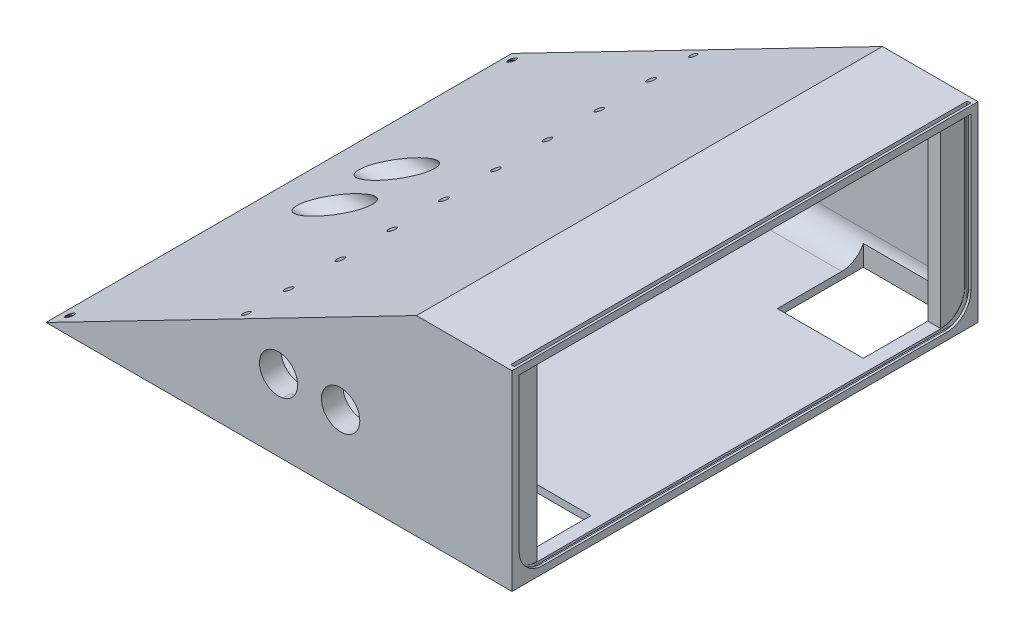
SolidWorks part; units mm, degrees
ref_plane "Front Plane" through (0, 0, 0) normal (0, 0, 1) x (1, 0, 0)
ref_plane "Top Plane" through (0, 0, 0) normal (0, 1, 0) x (1, 0, 0)
ref_plane "Right Plane" through (0, 0, 0) normal (1, 0, 0) x (0, 0, -1)
ref_plane "Plane1" through (0, 0, 0) normal (1, 0, 0) x (0, 0, -1)
ref_plane "Plane2" through (0, 0, 97.5) normal (0, 0, 1) x (1, 0, 0)
ref_plane "Plane3" through (1, 0, 0) normal (1, 0, 0) x (0, 0, -1)
ref_plane "Plane11" through (26, 0, 0) normal (1, 0, 0) x (0, 0, -1)
sketch "Sketch2" plane through (0, 0, 0) normal (0, 0, 1) x (1, 0, 0)
  line L0 (0, 0) -> (195, 0)
  line L1 (195, 0) -> (195, 80)
  line L2 (195, 80) -> (155, 80)
  line L3 (155, 80) -> (0, 0)
  dimension "D1" = 195
  dimension "D2" = 40
  dimension "80" = 80
extrude "Robot" add sketch "Sketch2" along normal blind 195
sketch "Sketch3" plane through (0, 0, 195) normal (0, 0, 1) x (1, 0, 0)
  line L0 (0, 0) -> (195, 0) construction
  circle A0 centre (97.2899, 30) radius 8.02
  circle A1 centre (123.2899, 30) radius 8.02
  dimension "D1" = 30
  dimension "D2" = 16.04
  dimension "D4" = 16.04
  dimension "D3" = 26
  dimension "D5" = 30
sketch "Arriba" plane through (0, 80, 0) normal (0, 1, 0) x (1, 0, 0)
  line L0 (195, 0) -> (195, -195) construction
  line L1 (0, 0) -> (0, -195) construction
  line L2 (0, -97.5) -> (195, -97.5) construction
  line L3 (0, 0) -> (195, 0) construction
  line L4 (0, -195) -> (195, -195) construction
  line L5 (97.5, 0) -> (97.5, -195) construction
sketch "Adelante" plane through (0, 0, 0) normal (1, 0, 0) x (0, 0, -1)
  line L0 (0, 80) -> (0, 0) construction
  line L1 (-97.5, 80) -> (-97.5, 0) construction
  line L2 (0, 80) -> (-195, 80) construction
  line L3 (-195, 0) -> (0, 0) construction
  line L4 (-195, 80) -> (-195, 0) construction
  line L5 (0, 0) -> (-195, 0) construction
sketch "Sketch9" plane through (0, 0, 0) normal (0, 0, -1) x (-1, 0, 0)
  line L1 (0, 0) -> (-195, 0) construction
  circle A0 centre (-97.284, 30) radius 8.2
  circle A1 centre (-123.284, 30) radius 8.2
  dimension "D2" = 16.4
  dimension "D4" = 30
  dimension "D6" = 16.4
  dimension "D3" = 30
  dimension "D5" = 26
sketch "Sketch10" plane through (0, 0, 0) normal (0, -1, 0) x (-1, 0, 0)
  line L0 (0, -195) -> (-195, -195) construction
  line L1 (-187, -191) -> (-150, -191)
  line L2 (-187, -191) -> (-187, -154)
  line L3 (-187, -154) -> (-150, -154)
  line L4 (-150, -191) -> (-150, -154)
  line L5 (-195, 0) -> (-195, -195) construction
  dimension "D1" = 4
  dimension "D2" = 8
  dimension "D3" = 37
  dimension "D4" = 37
sketch "Sketch12" plane through (0, 0, 0) normal (0, -1, 0) x (-1, 0, 0)
  line L0 (-195, 0) -> (-195, -195) construction
  line L1 (-187, -40) -> (-151, -40)
  line L2 (-187, -40) -> (-187, -4)
  line L3 (-187, -4) -> (-151, -4)
  line L4 (-151, -40) -> (-151, -4)
  line L5 (0, 0) -> (-195, 0) construction
  dimension "D1" = 8
  dimension "D2" = 4
  dimension "D3" = 36
  dimension "D4" = 36
sketch "Sketch13" plane through (0, 0, 0) normal (0, -1, 0) x (1, 0, 0)
  line L0 (0, 0) -> (195, 0) construction
  line L1 (26, 8) -> (33.1, 8)
  line L2 (26, 8) -> (26, 15.1)
  line L3 (26, 15.1) -> (33.1, 15.1)
  line L4 (33.1, 8) -> (33.1, 15.1)
  line L5 (0, 0) -> (0, 195) construction
  dimension "D1" = 8
  dimension "D2" = 26
  dimension "D3" = 7.1
  dimension "D4" = 7.1
sketch "Sketch14" plane through (0, 0, 0) normal (0, -1, 0) x (-1, 0, 0)
  line L0 (0, -195) -> (-195, -195) construction
  line L1 (-26, -179.9) -> (-33.1, -179.9)
  line L2 (-26, -179.9) -> (-26, -187)
  line L3 (-26, -187) -> (-33.1, -187)
  line L4 (-33.1, -179.9) -> (-33.1, -187)
  line L5 (0, 0) -> (0, -195) construction
  dimension "D1" = 8
  dimension "D2" = 26
  dimension "D3" = 7.1
  dimension "D4" = 7.1
sketch "Sketch15" plane through (0, 0, 0) normal (0, -1, 0) x (-1, 0, 0)
  line L0 (0, -97.5) -> (-195, -97.5) construction
  line L1 (-26, -93.95) -> (-33.1, -93.95)
  line L2 (-26, -93.95) -> (-26, -101.05)
  line L3 (-26, -101.05) -> (-33.1, -101.05)
  line L4 (-33.1, -93.95) -> (-33.1, -101.05)
  line L5 (0, 0) -> (0, -195) construction
  dimension "D1" = 3.55
  dimension "D2" = 3.55
  dimension "D3" = 7.1
  dimension "D4" = 26
shell "Vacio por dentro 3mm" thickness 3 removed face at (195, 40, 97.5)
extrude "Ultrasonico Derecha" cut sketch "Sketch3" against normal blind 3
sketch "Ultrasonico Centro " plane through (0, 0, 0) normal (1, 0, 0) x (0, 0, -1)
  line L0 (0, 0) -> (-195, 0) construction
  line L1 (-97.5, 80) -> (-97.5, 0) construction
  circle A0 centre (-85, 19) radius 8.7
  circle A1 centre (-111, 19) radius 8.7
  dimension "D2" = 17.4
  dimension "D4" = 17.4
  dimension "D1" = 19
  dimension "D3" = 12.5
  dimension "D5" = 13.5
  dimension "D6" = 19
extrude "Ultrasonico Izquierda" cut sketch "Sketch9" against normal blind 3
extrude "Cut-Extrude4" cut sketch "Ultrasonico Centro " along normal blind 75
sketch "Sketch16" plane through (0, 0, 195) normal (0, 0, 1) x (1, 0, 0)
  circle A0 centre (123.2899, 30) radius 8.02
  circle A1 centre (123.2899, 30) radius 8.6857
  circle A2 centre (97.3351, 30.0107) radius 8.6857
  circle A3 centre (97.3351, 30.0107) radius 8.02
extrude "Boss-Extrude1" add sketch "Sketch16" against normal blind 9
sketch "Sketch18" plane through (1, 0, 0) normal (1, 0, 0) x (0, 0, -1)
  circle A0 centre (-85, 19) radius 8.7
  circle A1 centre (-85, 19) radius 8.2
  circle A2 centre (-111, 19) radius 8.7192
  circle A3 centre (-111, 19) radius 8.2
  dimension "D1" = 17.4
  dimension "D2" = 16.4
  dimension "D3" = 16.4
  dimension "D4" = 17.4384
extrude "Boss-Extrude2" add sketch "Sketch18" along normal blind 60
mirror "Mirror1" about plane through (0, 0, 97.5) normal (0, 0, 1) of "Boss-Extrude1"
extrude "Rueda Derecha" cut sketch "Sketch10" against normal blind 3
extrude "Rueda Izquierda" cut sketch "Sketch12" against normal blind 3
extrude "Cyn70 Derecha" cut sketch "Sketch14" against normal blind 4
extrude "Cny70 Centro" cut sketch "Sketch15" against normal blind 4
extrude "Cny70 Izquierda" cut sketch "Sketch13" against normal blind 4
fillet "Rdondeo" radius 10 2 edges at (103.6768, 3, 3) (103.6768, 3, 192)
ref_plane "Plane4" through (0, 0, 0) normal (-0.4586, 0.8886, 0) x (0.8886, 0.4586, 0)
sketch "Sketch23" plane through (0, 0, 0) normal (-0.4586, 0.8886, 0) x (0.8886, 0.4586, 0)
  line L1 (0, -64.3188) -> (76.5925, -64.3188)
  line L2 (0, -64.3188) -> (0, -130.2867)
  line L3 (0, -130.2867) -> (76.5925, -130.2867)
  line L4 (76.5925, -64.3188) -> (76.5925, -130.2867)
extrude "Cut-Extrude5" cut sketch "Sketch23" along normal blind 25
sketch "Sketch24" plane through (0, 80, 0) normal (0, 1, 0) x (1, 0, 0)
  line L0 (195, 0) -> (155, 0) construction
  line L1 (192.5, -2) -> (194, -2)
  line L2 (192.5, -2) -> (192.5, -193)
  line L3 (192.5, -193) -> (194, -193)
  line L4 (194, -2) -> (194, -193)
  line L5 (195, -195) -> (155, -195) construction
  line L6 (195, -195) -> (195, 0) construction
  dimension "D1" = 2
  dimension "D2" = 2
  dimension "D3" = 1.5
  dimension "D4" = 1
extrude "Cut-Extrude6" cut sketch "Sketch24" against normal blind 78
sketch "Sketch25" plane through (0, 3, 0) normal (0, 1, 0) x (1, 0, 0)
  line L1 (187, -13) -> (192.3997, -13)
  line L2 (187, -13) -> (187, -0.907)
  line L3 (187, -0.907) -> (192.3997, -0.907)
  line L4 (192.3997, -13) -> (192.3997, -0.907)
extrude "Boss-Extrude3" add sketch "Sketch25" along normal blind 75
mirror "Mirror2" about plane through (0, 0, 97.5) normal (0, 0, 1) of "Boss-Extrude3"
ref_plane "Plane5" through (0, 3, 0) normal (0, -1, 0) x (-1, 0, 0)
ref_plane "Plane6" through (0, 0, 0) normal (0, 1, 0) x (1, 0, 0)
ref_plane "Plane10" through (0, 13.25, 0) normal (0, 1, 0) x (1, 0, 0)
ref_plane "Plane13" through (0, 5, 0) normal (0, 1, 0) x (1, 0, 0)
ref_plane "Plane7" through (97.5, 0, 0) normal (1, 0, 0) x (0, 0, -1)
ref_plane "Plane12" through (0, 30, 0) normal (0, 1, 0) x (1, 0, 0)
sketch "Sketch33" plane through (0, 0, 0) normal (0, 1, 0) x (1, 0, 0)
  line L0 (0, -195) -> (195, -195) construction
  line L1 (195, -195) -> (195, 0) construction
  circle A0 centre (190, -190) radius 1.5
  point P0 (190, -190)
  dimension "D1" = 3
  dimension "D2" = 5
  dimension "D3" = 5
hole_wizard "Avellanado para tornillo con cabeza plana de M31" positions "3DSketch5" profile "Sketch37" countersink size "M3" standard "Ansi Metric"
sketch3d "3DSketch5"
  point P0 (190, 0, 190)
sketch "Sketch37" plane through (190, 0, 190) normal (1, 0, 0) x (0, 0, -1)
  line L0 (0, 0) -> (0, 10.9614)
  line L1 (0, 10.9614) -> (1.6, 10)
  line L2 (1.6, 10) -> (1.6, 1.55)
  line L3 (1.6, 1.55) -> (3.15, 0)
  line L5 (3.15, 0) -> (0, 0)
  line L6 (-1.6, 1.55) -> (-3.15, 0) construction
  line L10 (0, 10.9614) -> (-1.6, 10) construction
  line L11 (0, -6.35) -> (0, 107.95) construction
  dimension "Diámetro de taladro" = 3.2
  dimension "Profundidad de taladro" = 10
  dimension "Ángulo de avellanado cercano" = 6.3
  dimension "Ángulo de avellanado lejano" = 90
  dimension "Ángulo de perforador" = 118
mirror "Mirror4" about plane through (0, 0, 97.5) normal (0, 0, 1) of "Avellanado para tornillo con cabeza plana de M31"
mirror "Mirror5" about plane through (97.5, 0, 0) normal (1, 0, 0) of "Mirror4", "Avellanado para tornillo con cabeza plana de M31"
sketch "Sketch38" plane through (0, 0, 0) normal (0, 1, 0) x (1, 0, 0)
  line L1 (26.0733, -187.1642) -> (33.1, -187.1642)
  line L2 (26.0733, -187.1642) -> (26.0733, -179.9)
  line L3 (26.0733, -179.9) -> (33.1, -179.9)
  line L4 (33.1, -187.1642) -> (33.1, -179.9)
  line L5 (26.0733, -101.5352) -> (33.1, -101.5352)
  line L6 (26.0733, -101.5352) -> (26.0733, -93.95)
  line L7 (26.0733, -93.95) -> (33.1, -93.95)
  line L8 (33.1, -101.5352) -> (33.1, -93.95)
  line L9 (26.0733, -15.3065) -> (33.1, -15.3065)
  line L10 (26.0733, -15.3065) -> (26.0733, -8)
  line L11 (26.0733, -8) -> (33.1, -8)
  line L12 (33.1, -15.3065) -> (33.1, -8)
  line L13 (25.5733, -7.5) -> (33.6, -7.5)
  line L14 (25.5733, -7.5) -> (25.5733, -15.8065)
  line L15 (25.5733, -15.8065) -> (33.6, -15.8065)
  line L16 (33.6, -7.5) -> (33.6, -15.8065)
  line L17 (25.5733, -93.45) -> (33.6, -93.45)
  line L18 (25.5733, -93.45) -> (25.5733, -102.0352)
  line L19 (25.5733, -102.0352) -> (33.6, -102.0352)
  line L20 (33.6, -93.45) -> (33.6, -102.0352)
  line L21 (25.5733, -179.4) -> (33.6, -179.4)
  line L22 (25.5733, -179.4) -> (25.5733, -187.6642)
  line L23 (25.5733, -187.6642) -> (33.6, -187.6642)
  line L24 (33.6, -179.4) -> (33.6, -187.6642)
  point P16 (25.5733, -11.6532)
  dimension "D1" = 0.5
  dimension "D2" = 0.5
  dimension "D3" = 0.5
  dimension "D4" = 0.5
  dimension "D5" = 0.5
  dimension "D6" = 0.5
  dimension "D7" = 0.5
  dimension "D8" = 0.5
  dimension "D9" = 0.5
  dimension "D10" = 0.5
  dimension "D11" = 0.5
  dimension "D12" = 0.5
extrude "Boss-Extrude4" add sketch "Sketch38" along normal blind 6
sketch "Sketch40" plane through (0, 0, 0) normal (-0.4586, 0.8886, 0) x (0.8886, 0.4586, 0)
  line L1 (174.4276, 0) -> (0, 0) construction
  circle A0 centre (89.8771, -21.6667) radius 1.7
  circle A1 centre (89.8771, -43.3333) radius 1.7
  circle A2 centre (89.8771, -65) radius 1.7
  circle A3 centre (89.8771, -86.6667) radius 1.7
  circle A4 centre (89.8771, -4) radius 1.52
  dimension "D1" = 3.4
  dimension "D3" = 3.4
  dimension "D4" = 21.6667
  dimension "D5" = 3.4
  dimension "D6" = 21.6667
  dimension "D7" = 3.4
  dimension "D8" = 21.6667
  dimension "D9" = 4
  dimension "D10" = 3.04
  dimension "D2" = 21.6667
extrude "Agujeros rampa" cut sketch "Sketch40" against normal blind 3
mirror "Mirror7" about plane through (0, 0, 97.5) normal (0, 0, 1) of "Agujeros rampa"
